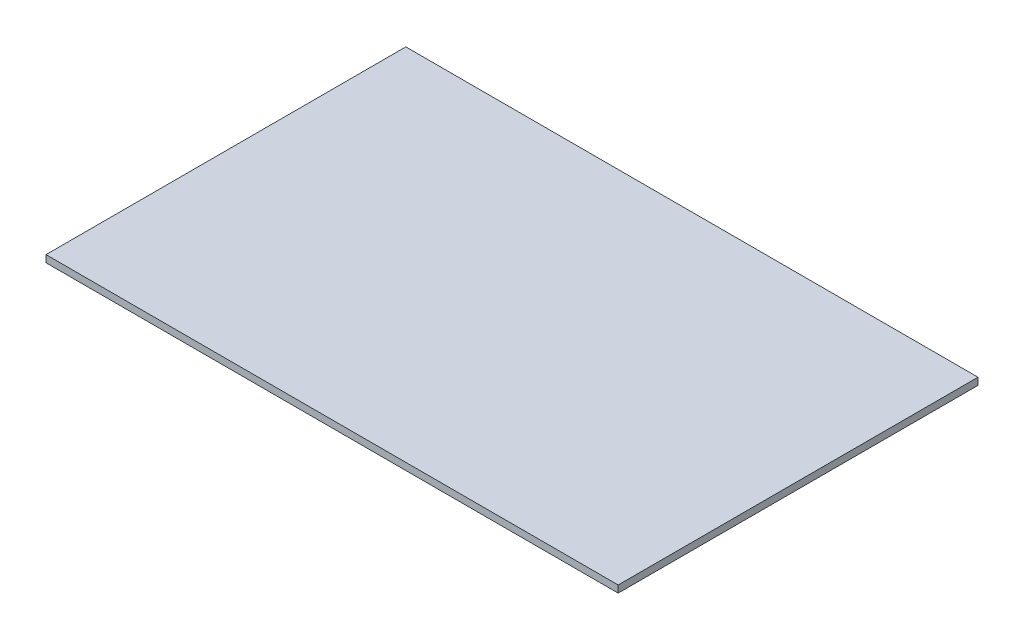
SolidWorks part; units mm, degrees
ref_plane "Front Plane" through (0, 0, 0) normal (0, 0, 1) x (1, 0, 0)
ref_plane "Top Plane" through (0, 0, 0) normal (0, 1, 0) x (1, 0, 0)
ref_plane "Right Plane" through (0, 0, 0) normal (1, 0, 0) x (0, 0, -1)
sketch "Sketch1" plane through (0, 0, 0) normal (0, 1, 0) x (1, 0, 0)
  line L1 (-677.3067, 361.6334) -> (292.6933, 361.6334)
  line L2 (-677.3067, 361.6334) -> (-677.3067, -248.3666)
  line L3 (-677.3067, -248.3666) -> (292.6933, -248.3666)
  line L4 (292.6933, 361.6334) -> (292.6933, -248.3666)
  dimension "D1" = 970
  dimension "D2" = 610
extrude "Boss-Extrude1" add sketch "Sketch1" along normal blind 12
